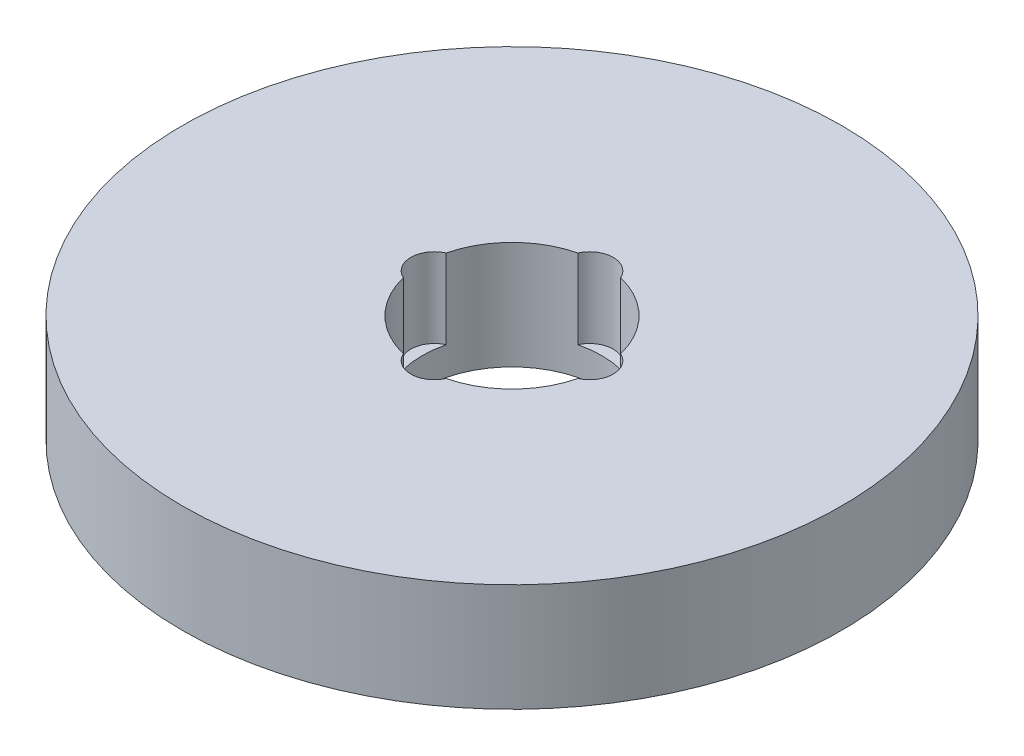
SolidWorks part; units mm, degrees
ref_plane "Front Plane" through (0, 0, 0) normal (0, 0, 1) x (1, 0, 0)
ref_plane "Top Plane" through (0, 0, 0) normal (0, 1, 0) x (1, 0, 0)
ref_plane "Right Plane" through (0, 0, 0) normal (1, 0, 0) x (0, 0, -1)
sketch "Sketch1" plane through (0, 0, 0) normal (0, 1, 0) x (1, 0, 0)
  circle A0 centre (0, 0) radius 82.5
  dimension "FLANGE_OD" = 165
extrude "Boss-Extrude1" add sketch "Sketch1" along normal blind 27
sketch "Sketch2" plane through (0, 0, 0) normal (0, 1, 0) x (1, 0, 0)
  circle A0 centre (0, 0) radius 22.5
  dimension "BORE_D" = 45
extrude "Cut-Extrude1" cut sketch "Sketch2" along normal through all
sketch "Sketch3" plane through (0, 27, 0) normal (0, 1, 0) x (1, 0, 0)
  circle A0 centre (0, 0) radius 19.4512 construction
  circle A1 centre (-19.4512, 0) radius 5.8675
  dimension "BOLT_D" = 11.735
  dimension "BOLT_PCD" = 38.9023
extrude "Cut-Extrude2" cut sketch "Sketch3" against normal blind 19.8967
pattern_circular "CirPattern1" count 4 over 360 about axis through (0, 0, 0) along (0, 1, 0) of "Cut-Extrude2"
